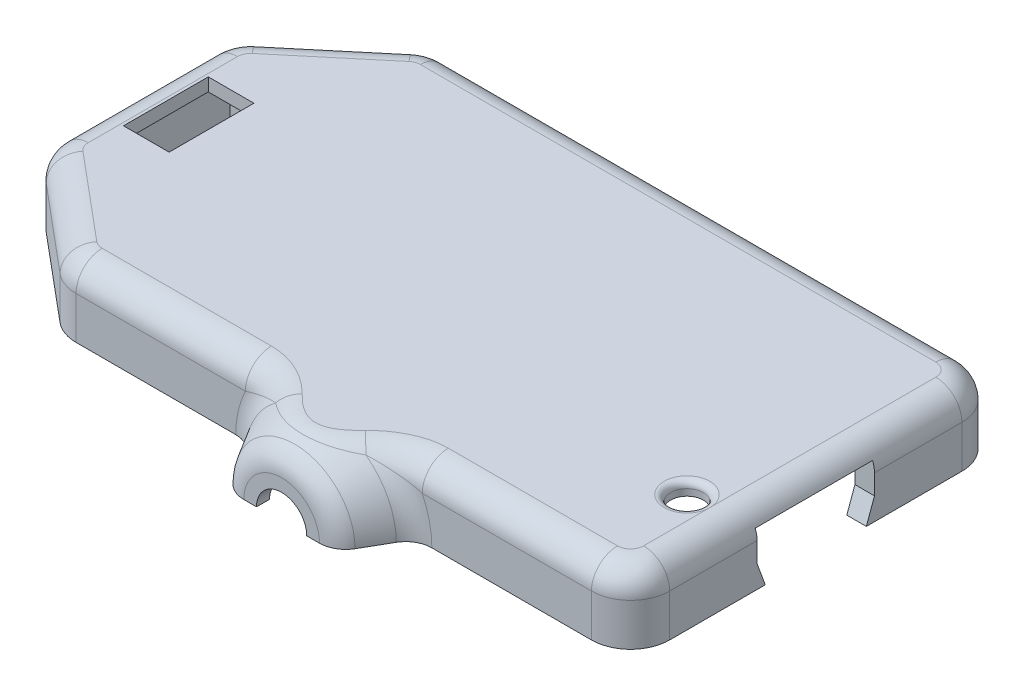
SolidWorks part; units mm, degrees
material "Nylon 101"
ref_plane "Front Plane" through (0, 0, 0) normal (0, 0, 1) x (1, 0, 0)
ref_plane "Top Plane" through (0, 0, 0) normal (0, 1, 0) x (1, 0, 0)
ref_plane "Right Plane" through (0, 0, 0) normal (1, 0, 0) x (0, 0, -1)
sketch "Sketch1" plane through (0, 0, 0) normal (0, 1, 0) x (1, 0, 0)
  line L61 (26.7755, -17.8683) -> (26.7755, 4.5317)
  line L65 (25.2755, 6.0317) -> (25.2755, -19.3683) construction
  line L68 (25.2755, -19.3683) -> (-15.3245, -19.3683) construction
  line L69 (-15.3245, -19.3683) -> (-15.3245, 6.0317) construction
  line L70 (-15.3245, 6.0317) -> (25.2755, 6.0317) construction
  line L73 (-17.6603, 6.8319) -> (-24.2004, 1.356)
  line L74 (-25.2745, -0.9442) -> (-25.2745, -12.3924)
  line L75 (-24.2004, -14.6926) -> (-17.6603, -20.1685)
  line L76 (-15.3245, -19.3683) -> (25.2755, 6.0317) construction
  line L77 (25.2755, -19.3683) -> (-15.3245, 6.0317) construction
  line L78 (-18.3245, -0.5433) -> (-18.3245, -12.7933) construction
  line L79 (-24.2745, -0.5433) -> (-18.3245, -0.5433) construction
  line L80 (-24.2745, -12.7933) -> (-24.2745, -0.5433) construction
  line L81 (-18.3245, -12.7933) -> (-24.2745, -12.7933) construction
  line L82 (-24.2745, -12.7933) -> (-18.3245, -0.5433) construction
  line L83 (-18.3245, -12.7933) -> (-24.2745, -0.5433) construction
  line L84 (-21.2995, -6.6683) -> (4.9755, -6.6683) construction
  line L87 (-15.7344, -17.8683) -> (-15.7344, 4.5317) construction
  line L88 (-15.7344, 4.5317) -> (23.7755, 4.5317) construction
  line L89 (23.7755, 4.5317) -> (23.7755, -17.8683) construction
  line L90 (23.7755, -17.8683) -> (-15.7344, -17.8683) construction
  line L91 (-15.7344, 7.5317) -> (23.7755, 7.5317)
  line L92 (-15.7344, -20.8683) -> (23.7755, -20.8683)
  arc A18 (23.7755, -20.8683) -> (26.7755, -17.8683) centre (23.7755, -17.8683) ccw
  arc A19 (26.7755, 4.5317) -> (23.7755, 7.5317) centre (23.7755, 4.5317) ccw
  arc A20 (-15.7344, 7.5317) -> (-17.6603, 6.8319) centre (-15.7344, 4.5317) ccw
  arc A21 (-24.2004, 1.356) -> (-25.2745, -0.9442) centre (-22.2745, -0.9442) ccw
  arc A22 (-25.2745, -12.3924) -> (-24.2004, -14.6926) centre (-22.2745, -12.3924) ccw
  arc A23 (-17.6603, -20.1685) -> (-15.7344, -20.8683) centre (-15.7344, -17.8683) ccw
  point P2 (4.9755, -6.6683)
  dimension "D11" = 3
  dimension "D2" = 52.05
  dimension "D3" = 1
  dimension "D4" = 5.95
  dimension "D5" = 12.25
  dimension "D6" = 25.4
  dimension "D7" = 3
  dimension "D8" = 1.5
extrude "Boss-Extrude1" add sketch "Sketch1" along normal blind 5.25
sketch "Sketch2" plane through (0, 0, 0) normal (0, 1, 0) x (1, 0, 0)
  line L0 (25.2755, 6.0317) -> (25.2755, -19.3683) construction
  line L1 (25.2755, -19.3683) -> (-15.3245, -19.3683) construction
  line L2 (-15.3245, -19.3683) -> (-15.3245, 6.0317) construction
  line L3 (-15.3245, 6.0317) -> (25.2755, 6.0317) construction
  line L4 (25.2755, 6.0317) -> (25.2755, -19.3683)
  line L5 (25.2755, -19.3683) -> (-15.3245, -19.3683)
  line L6 (-15.3245, -19.3683) -> (-15.3245, 6.0317)
  line L7 (-15.3245, 6.0317) -> (25.2755, 6.0317)
  line L8 (-18.3245, -12.7933) -> (-24.2745, -12.7933) construction
  line L9 (-18.3245, -0.5433) -> (-18.3245, -12.7933) construction
  line L10 (-24.2745, -0.5433) -> (-18.3245, -0.5433) construction
  line L11 (-24.2745, -12.7933) -> (-24.2745, -0.5433) construction
  line L12 (-18.3245, -12.7933) -> (-24.2745, -12.7933)
  line L13 (-18.3245, -0.5433) -> (-18.3245, -12.7933)
  line L14 (-24.2745, -0.5433) -> (-18.3245, -0.5433)
  line L15 (-24.2745, -12.7933) -> (-24.2745, -0.5433)
extrude "Cut-Extrude1" cut sketch "Sketch2" along normal blind 4.25
sketch "Sketch4" plane through (0, 5.25, 0) normal (0, 1, 0) x (1, 0, 0)
  line L1 (-23.0495, -9.9183) -> (-19.5495, -9.9183)
  line L2 (-23.0495, -9.9183) -> (-23.0495, -3.4183)
  line L3 (-23.0495, -3.4183) -> (-19.5495, -3.4183)
  line L4 (-19.5495, -9.9183) -> (-19.5495, -3.4183)
  line L5 (-23.0495, -9.9183) -> (-19.5495, -3.4183) construction
  line L6 (-23.0495, -3.4183) -> (-19.5495, -9.9183) construction
  point P0 (-21.2995, -6.6683)
  dimension "D1" = 6.5
  dimension "D2" = 3.5
extrude "Cut-Extrude2" cut sketch "Sketch4" against normal through all
sketch "Sketch5" plane through (0, 0, 0) normal (0, -1, 0) x (1, 0, 0)
  line L0 (-25.2745, 6.6683) -> (26.7755, 6.6683) construction
  line L1 (-25.2745, 0.9442) -> (-25.2745, 12.3924) construction
  line L2 (26.7755, 17.8683) -> (26.7755, -4.5317) construction
  circle A0 centre (-18.2745, 16.6683) radius 1
  circle A1 centre (-18.2745, -3.3317) radius 1
  dimension "D1" = 2
  dimension "D2" = 10
  dimension "D3" = 7
extrude "Boss-Extrude2" add sketch "Sketch5" along normal blind 3
fillet "Fillet2" radius 0.25 4 edges at (-18.2745, 0, -2.3317) (-18.2745, -3, -2.3317) (-18.2745, -3, 15.6683) (-18.2745, 0, 17.6683)
sketch "Sketch6" plane through (0, 0, 0) normal (0, -1, 0) x (1, 0, 0)
  line L0 (-12.2344, -6.7817) -> (-5.9844, -6.7817)
  line L4 (-15.3245, -6.0317) -> (25.2755, -6.0317)
  line L5 (25.2755, -6.0317) -> (25.2755, 19.3683)
  line L6 (25.2755, 19.3683) -> (-15.3245, 19.3683)
  line L7 (-15.3245, 19.3683) -> (-15.3245, -6.0317)
  line L8 (-12.2344, -6.0317) -> (-5.9844, -6.0317)
  line L12 (-12.2344, -6.0317) -> (-12.2344, -6.7817)
  line L13 (-5.9844, -6.0317) -> (-5.9844, -6.7817)
  line L14 (14.0255, -6.0317) -> (14.0255, -6.7817)
  line L15 (20.2755, -6.0317) -> (20.2755, -6.7817)
  line L16 (26.7755, 6.6683) -> (-25.2745, 6.6683) construction
  line L17 (-15.3245, -6.0317) -> (25.2755, -6.0317) construction
  line L18 (-16.0745, -6.7817) -> (26.0255, -6.7817) construction
  line L19 (-16.0745, 20.1183) -> (-16.0745, -6.7817) construction
  line L20 (-15.3245, 19.3683) -> (-15.3245, -6.0317) construction
  line L21 (14.0255, -6.0317) -> (20.2755, -6.0317)
  line L22 (14.0255, -6.7817) -> (20.2755, -6.7817)
  line L23 (25.2755, -6.0317) -> (25.2755, 19.3683) construction
  line L24 (26.0255, -6.7817) -> (26.0255, 20.1183) construction
  line L25 (25.2755, 19.3683) -> (-15.3245, 19.3683) construction
  line L26 (26.0255, 20.1183) -> (-16.0745, 20.1183) construction
  line L27 (-25.2745, 0.9442) -> (-25.2745, 12.3924) construction
  line L28 (26.7755, 17.8683) -> (26.7755, -4.5317) construction
  line L29 (14.0255, 20.1183) -> (20.2755, 20.1183)
  line L30 (14.0255, 19.3683) -> (20.2755, 19.3683)
  line L31 (20.2755, 19.3683) -> (20.2755, 20.1183)
  line L32 (14.0255, 19.3683) -> (14.0255, 20.1183)
  line L33 (-5.9844, 19.3683) -> (-5.9844, 20.1183)
  line L34 (-12.2344, 19.3683) -> (-12.2344, 20.1183)
  line L35 (-12.2344, 19.3683) -> (-5.9844, 19.3683)
  line L36 (-12.2344, 20.1183) -> (-5.9844, 20.1183)
  dimension "D3" = 6.25
  dimension "D4" = 6.25
  dimension "D5" = 3.5
  dimension "D6" = 3.5
  dimension "D1" = 0
  dimension "D2" = 0.75
extrude "Cut-Extrude3" cut sketch "Sketch6" against normal up to surface (4.25 mm away) up to face at (4.9755, 4.25, 6.6683)
fillet "Fillet3" radius 0.25 8 edges at (14.0255, 2.125, -6.0317) (20.2755, 2.125, -6.0317) (-5.9844, 2.125, -6.0317) (-12.2344, 2.125, -6.0317) (20.2755, 2.125, 19.3683) (14.0255, 2.125, 19.3683) (-5.9844, 2.125, 19.3683) (-12.2344, 2.125, 19.3683)
sketch "Sketch8" plane through (26.7755, 0, 0) normal (1, 0, 0) x (0, 0, -1)
  line L0 (-10.5433, 0) -> (-2.7933, 0)
  line L1 (-17.8683, 0) -> (4.5317, 0) construction
  line L2 (-2.7933, 0) -> (-2.1683, 1.7172)
  line L3 (-2.1683, 1.7172) -> (-2.1683, 4)
  line L4 (-2.1683, 4) -> (-11.1683, 4)
  line L5 (-11.1683, 4) -> (-11.1683, 1.7172)
  line L6 (-11.1683, 1.7172) -> (-10.5433, 0)
  line L7 (-6.6683, 0) -> (-6.6683, 11.7915) construction
  line L8 (-17.8683, 5.25) -> (-17.8683, 0) construction
  line L9 (4.5317, 5.25) -> (4.5317, 0) construction
  dimension "D1" = 9
  dimension "D2" = 20
  dimension "D3" = 7.75
  dimension "D4" = 4
extrude "Cut-Extrude5" cut sketch "Sketch8" against normal blind 4
sketch "Sketch9" plane through (0, 0, 20.8683) normal (0, 0, 1) x (1, 0, 0)
  line L0 (-15.7344, 0) -> (23.7755, 0) construction
  line L1 (-0.4745, 4.5) -> (8.5255, 4.5) construction
  line L2 (-0.4745, 4.5) -> (-0.4745, 0) construction
  line L3 (-0.4745, 0) -> (8.5255, 0) construction
  line L4 (8.5255, 4.5) -> (8.5255, 0) construction
  circle A0 centre (4.0255, 0) radius 6.364
  point P6 (4.0255, 0)
  dimension "D1" = 9
  dimension "D2" = 4.5
  dimension "D3" = 19.35
extrude "Boss-Extrude3" add sketch "Sketch9" along normal blind 4 draft 30 and the other way up to surface (1.5 mm away)
sketch "Sketch10" plane through (0, 0, 19.3683) normal (0, 0, -1) x (-1, 0, 0)
  line L0 (-8.9965, 5.25) -> (0.9454, 5.25)
  line L1 (-23.7755, 5.25) -> (15.7344, 5.25) construction
  circle A0 centre (-4.0255, 0) radius 7.23 construction
  arc A1 (0.9454, 5.25) -> (-8.9965, 5.25) centre (-4.0255, 0) ccw
extrude "Cut-Extrude6" cut sketch "Sketch10" against normal blind 4
sketch "Sketch11" plane through (0, 0, 19.3683) normal (0, 0, -1) x (-1, 0, 0)
  line L0 (0.4745, 0) -> (-8.5255, 0) construction
  line L1 (-7.2755, 0) -> (-0.7755, 0)
  line L2 (-7.2755, 0) -> (-7.2755, 3.25)
  line L3 (-7.2755, 3.25) -> (-0.7755, 3.25)
  line L4 (-0.7755, 0) -> (-0.7755, 3.25)
  line L5 (-8.5255, 4.5) -> (-8.5255, 0) construction
  dimension "D1" = 3.25
  dimension "D2" = 6.5
  dimension "D3" = 1.25
extrude "Cut-Extrude7" cut sketch "Sketch11" against normal blind 4.5
sketch "Sketch12" plane through (0, 0, 24.8683) normal (0, 0, 1) x (1, 0, 0)
  circle A0 centre (4.0255, 0) radius 1.925
  dimension "D1" = 3.85
extrude "Cut-Extrude8" cut sketch "Sketch12" against normal blind 4
sketch "Sketch13" plane through (0, 0, 19.3683) normal (0, 0, -1) x (-1, 0, 0)
  line L0 (-10.3895, 0) -> (2.3384, 0)
  circle A0 centre (-4.0255, 0) radius 6.364 construction
  arc A1 (-10.3895, 0) -> (2.3384, 0) centre (-4.0255, 0) ccw
extrude "Cut-Extrude9" cut sketch "Sketch13" against normal through all
fillet "Fillet4" radius 2 17 edges at (15.699, 5.25, 20.8683) (25.8968, 5.25, 19.9896) (26.7755, 5.25, 6.6683) (25.8968, 5.25, -6.653) (4.0206, 5.25, -7.5317) (-16.7589, 5.25, -7.3513) (-20.9303, 5.25, -4.094) (-24.9927, 5.25, -0.3251) (-25.2745, 5.25, 6.6683) (-24.9927, 5.25, 13.6617) (-7.6529, 5.25, 20.8683) (-16.7589, 5.25, 20.6879) (4.3723, 5.25, 22.7779) (9.6554, 2.9673, 20.8683) (-1.6043, 2.9673, 20.8683) (4.0255, 4.0546, 24.8683) (-20.9303, 5.25, 17.4306)
sketch "Sketch14" plane through (0, 4.25, 0) normal (0, -1, 0) x (1, 0, 0)
  line L1 (25.2755, 2.7933) -> (26.7755, 2.7933) construction
  line L2 (7.665, 6.6683) -> (27.665, 6.6683) construction
  line L3 (25.2755, 10.5433) -> (26.7755, 10.5433) construction
  line L4 (25.2755, 19.3683) -> (25.2755, 10.5433) construction
  circle A1 centre (23.0255, 12.7933) radius 1.25
  dimension "D2" = 2.5
  dimension "D1" = 20
  dimension "D3" = 2.25
  dimension "D4" = 2.25
extrude "Cut-Extrude10" cut sketch "Sketch14" against normal through all
sketch "Sketch15" plane through (0, 4.25, 0) normal (0, -1, 0) x (1, 0, 0)
  line L0 (-19.5495, 9.9183) -> (-23.0495, 9.9183) construction
  line L1 (-23.0495, 3.4183) -> (-19.5495, 3.4183) construction
  line L2 (-21.2995, 11.4183) -> (-21.2995, 1.9183) construction
  line L3 (-23.0495, 9.9183) -> (-23.0495, 3.4183) construction
  line L4 (-19.5495, 3.4183) -> (-19.5495, 9.9183) construction
  circle A0 centre (-21.2995, 11.4183) radius 0.75
  circle A1 centre (-21.2995, 1.9183) radius 0.75
  dimension "D1" = 1.5
  dimension "D2" = 1.5
  dimension "D3" = 1.5
extrude "Cut-Extrude11" cut sketch "Sketch15" against normal blind 0.5
fillet "Fillet5" radius 0.5 3 edges at (-21.2995, 4.25, 1.1683) (-21.2995, 4.25, 10.6683) (23.0255, 5.25, 14.0433)
equation "\"D3@Sketch11\"=(9-6.5)/2"
equation "\"D3@Sketch14\"=1.25+1"
